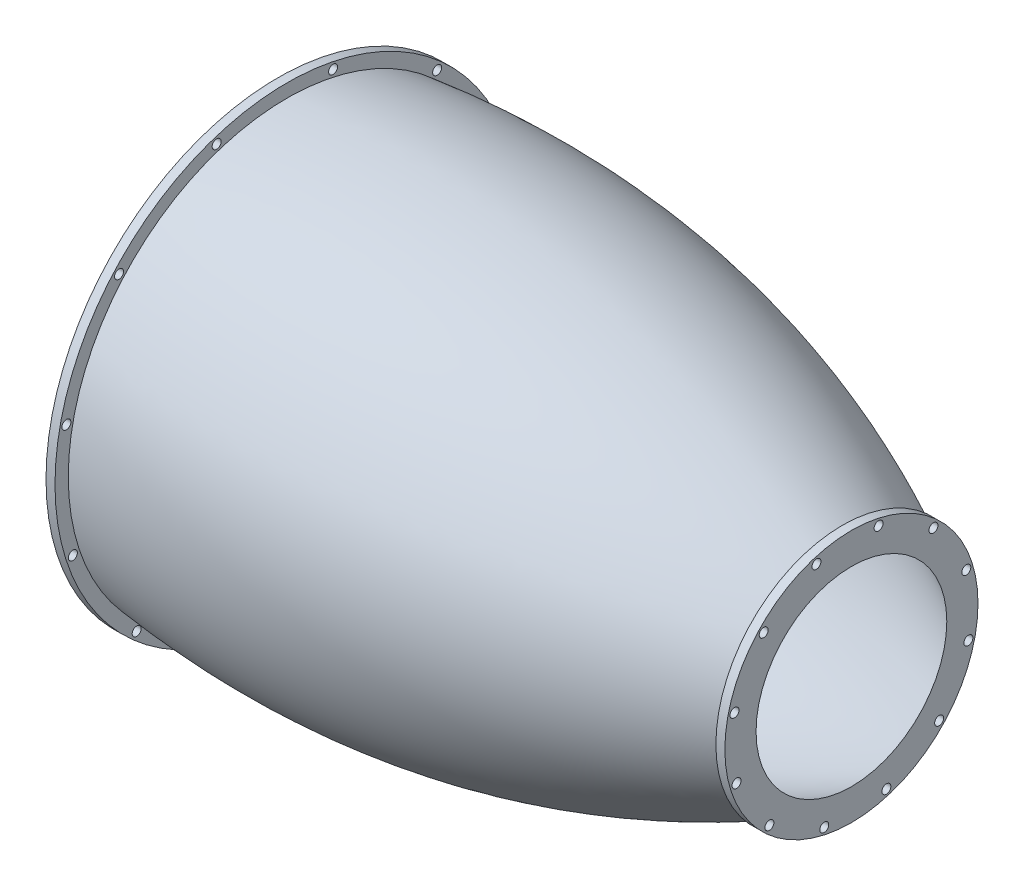
SolidWorks part; units mm, degrees
material "Copper"
ref_plane "Front Plane" through (0, 0, 0) normal (0, 0, 1) x (1, 0, 0)
ref_plane "Top Plane" through (0, 0, 0) normal (0, 1, 0) x (1, 0, 0)
ref_plane "Right Plane" through (0, 0, 0) normal (1, 0, 0) x (0, 0, -1)
sketch "Sketch1" plane through (0, 0, 0) normal (0, 0, 1) x (1, 0, 0)
  line L0 (-1229.8282, 0) -> (1426.3964, 0) construction
  line L1 (0, -63.5) -> (0, 63.5) construction
  line L2 (0, 0) -> (500, 0) construction
  line L3 (500, -330.2) -> (500, 330.2) construction
  line L5 (500, 339.09) -> (500, 330.2)
  line L6 (0, -72.39) -> (0, -63.5)
  line L7 (500, -339.09) -> (500, -330.2)
  line L8 (-412.8242, -144.8099) -> (-412.8242, 144.8099) construction
  line L9 (-412.8242, 144.8099) -> (-412.8242, 153.6999)
  line L10 (-412.8242, -144.8099) -> (-412.8242, -153.6999)
  spline S0 degree 2 poles (0, 63.5) (163.7773, 321.6338) (500, 330.2) knots 0 0 0 1 1 1
  spline S1 degree 2 poles (0, -63.5) (163.7773, -321.6338) (500, -330.2) knots 0 0 0 1 1 1
  spline S2 degree 2 poles (0, -72.39) (163.7773, -330.5238) (500, -339.09) knots 0 0 0 1 1 1
  spline S3 degree 2 poles (0, -63.5) (163.7773, -321.6338) (500, -330.2) knots 0 0 0 1 1 1
  spline S4 degree 2 poles (0, 72.39) (163.7773, 330.5238) (500, 339.09) knots 0 0 0 1 1 1
  spline S5 degree 2 poles (0, 63.5) (-192.2835, 162.6782) (-412.8242, 144.8099) knots 0 0 0 1 1 1
  spline S6 degree 2 poles (0, -63.5) (-192.2835, -162.6782) (-412.8242, -144.8099) knots 0 0 0 1 1 1
  spline S7 degree 2 poles (0, -72.39) (-189.3535, -181.7828) (-412.8242, -153.6999) knots 0 0 0 1 1 1
  spline S9 degree 2 poles (0, 72.39) (-189.3535, 181.7828) (-412.8242, 153.6999) knots 0 0 0 1 1 1
  point P8 (0, 0)
  point P14 (500, 0)
  point P22 (-412.8242, 0)
  point P23 (-211.74, -176.3734)
  point P27 (-211.74, 164.9699)
  point P29 (-138.8007, 118.7994)
  point P30 (-138.8007, 132.7516)
  dimension "D4" = 8.89
  dimension "D1" = 127
  dimension "D2" = 500
  dimension "D3" = 660.4
  dimension "D5" = 8.89
  dimension "D6" = 8.89
  dimension "D7" = 289.6197
revolve "Revolve3" add sketch "Sketch1" angle 360 about L0 region at (490.4648, 334.645, 0)
ref_plane "Plane1" through (0, 0, 0) normal (1, 0, 0) x (0, 0, -1)
ref_plane "Plane2" through (-7.62, 0, 0) normal (-1, 0, 0) x (0, 0, 1)
sketch "Sketch4" plane through (-7.62, 0, 0) normal (-1, 0, 0) x (0, 0, 1)
  line L1 (-1213.2286, 638.9142) -> (1085.9115, 638.9142)
  line L2 (-1213.2286, 638.9142) -> (-1213.2286, -445.9528)
  line L3 (-1213.2286, -445.9528) -> (1085.9115, -445.9528)
  line L4 (1085.9115, 638.9142) -> (1085.9115, -445.9528)
  point P4 (1085.9115, 638.9142)
  point P5 (-1213.2286, -445.9528)
extrude "Cut-Extrude1" cut sketch "Sketch4" against normal blind 782.066
ref_plane "Plane3" through (-7.62, 0, 0) normal (1, 0, 0) x (0, 0, -1)
sketch "Sketch5" plane through (-7.62, 0, 0) normal (1, 0, 0) x (0, 0, -1)
  circle A0 centre (0, 0) radius 76.7288 construction
  circle A1 centre (0, 0) radius 76.7288
  circle A2 centre (0, 0) radius 89.4288
  dimension "D1" = 12.7
extrude "Boss-Extrude1" add sketch "Sketch5" against normal blind 6.35
ref_plane "Plane4" through (-412.8242, 0, 0) normal (-1, 0, 0) x (0, 0, 1)
sketch "Sketch6" plane through (-412.8242, 0, 0) normal (-1, 0, 0) x (0, 0, 1)
  circle A0 centre (0, 0) radius 153.6999 construction
  circle A1 centre (0, 0) radius 153.6999
  circle A2 centre (0, 0) radius 163.8599
  dimension "D1" = 10.16
extrude "Boss-Extrude2" add sketch "Sketch6" against normal blind 6.35 contours A2 | A1
ref_plane "Plane5" through (-13.97, 0, 0) normal (-1, 0, 0) x (0, 0, 1)
sketch "Sketch7" plane through (-13.97, 0, 0) normal (-1, 0, 0) x (0, 0, 1)
  line L0 (0, 0) -> (20.2302, -87.1106) construction
  line L1 (20.2302, -87.1106) -> (18.1534, -78.168) construction
  circle A1 centre (0, 0) radius 89.4288
  circle A2 centre (0, 0) radius 89.4288
  circle A3 centre (0, 0) radius 80.2482 construction
  circle A4 centre (0, 0) radius 80.2482
  point P7 (19.1918, -82.6393)
  dimension "D1" = 0
hole_wizard "1/4 (0.25) Diameter Hole1" positions "3DSketch1" profile "Sketch8" hole size "1/4" standard "ANSI Inch"
sketch3d "3DSketch1"
  point P0 (-13.97, -82.6393, 19.1918)
sketch "Sketch8" plane through (-13.97, -82.6393, 19.1918) normal (0, 1, 0) x (0, 0, 1)
  line L0 (0, 0) -> (0, 8.2577)
  line L1 (0, 8.2577) -> (3.175, 6.35)
  line L2 (3.175, 6.35) -> (3.175, 0)
  line L5 (3.175, 0) -> (0, 0)
  line L10 (0, 8.2577) -> (-3.175, 6.35) construction
  line L11 (0, -6.35) -> (0, 107.95) construction
  dimension "Hole Dia." = 6.35
  dimension "Hole Depth" = 6.35
  dimension "Drill Angle" = 118
pattern_circular "CirPattern1" count 12 over 360 about axis through (-13.97, 0, 0) along (1, 0, 0) of "1/4 (0.25) Diameter Hole1" reverse direction yes
ref_plane "Plane6" through (-406.4742, 0, 0) normal (1, 0, 0) x (0, 0, -1)
sketch "Sketch9" plane through (-406.4742, 0, 0) normal (1, 0, 0) x (0, 0, -1)
  line L0 (0, 0) -> (-33.5856, -160.381) construction
  line L1 (-33.5856, -160.381) -> (-31.6611, -151.1914) construction
  circle A0 centre (0, 0) radius 163.8599 construction
  circle A1 centre (0, 0) radius 163.8599
  circle A2 centre (0, 0) radius 154.4709 construction
  circle A3 centre (0, 0) radius 154.4709
  point P6 (-32.6234, -155.7862)
hole_wizard "1/4 (0.25) Diameter Hole2" positions "3DSketch2" profile "Sketch10" hole size "1/4" standard "ANSI Inch"
sketch3d "3DSketch2"
  point P0 (-406.4742, -155.7862, 32.6234)
sketch "Sketch10" plane through (-406.4742, -155.7862, 32.6234) normal (0, 1, 0) x (0, 0, -1)
  line L0 (0, 0) -> (0, 8.2577)
  line L1 (0, 8.2577) -> (3.175, 6.35)
  line L2 (3.175, 6.35) -> (3.175, 0)
  line L5 (3.175, 0) -> (0, 0)
  line L10 (0, 8.2577) -> (-3.175, 6.35) construction
  line L11 (0, -6.35) -> (0, 107.95) construction
  dimension "Hole Dia." = 6.35
  dimension "Hole Depth" = 6.35
  dimension "Drill Angle" = 118
pattern_circular "CirPattern2" count 12 over 360 about axis through (-406.4742, 0, 0) along (-1, 0, 0) of "1/4 (0.25) Diameter Hole2" reverse direction yes
